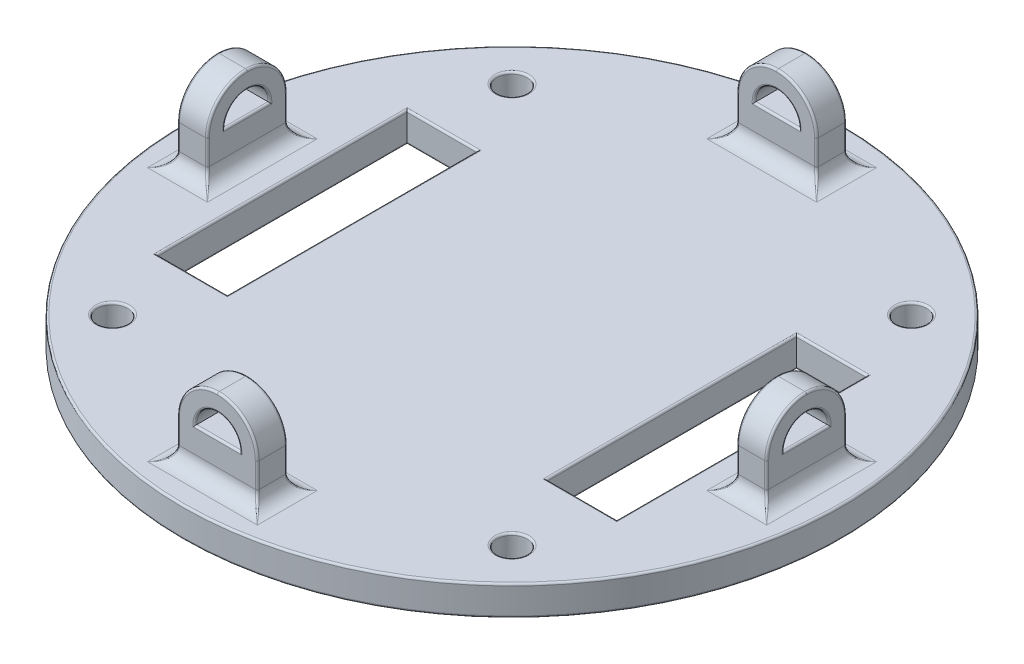
SolidWorks part; units mm, degrees
ref_plane "Front Plane" through (0, 0, 0) normal (0, 0, 1) x (1, 0, 0)
ref_plane "Top Plane" through (0, 0, 0) normal (0, 1, 0) x (1, 0, 0)
ref_plane "Right Plane" through (0, 0, 0) normal (1, 0, 0) x (0, 0, -1)
sketch "Sketch1" plane through (0, 0, 0) normal (0, 1, 0) x (1, 0, 0)
  circle A0 centre (0, 0) radius 33
  dimension "D1" = 66
extrude "Boss-Extrude1" add sketch "Sketch1" along normal blind 3
sketch "Sketch2" plane through (0, 3, 0) normal (0, 1, 0) x (1, 0, 0)
  line L0 (0, -6.05) -> (0, 6.05) construction
  line L1 (-23, 12.5) -> (-16, 12.5)
  line L2 (-23, 12.5) -> (-23, -12.5)
  line L3 (-23, -12.5) -> (-16, -12.5)
  line L4 (-16, 12.5) -> (-16, -12.5)
  line L9 (16, 12.5) -> (16, -12.5)
  line L10 (23, -12.5) -> (16, -12.5)
  line L11 (23, 12.5) -> (23, -12.5)
  line L12 (23, 12.5) -> (16, 12.5)
  point P8 (-16, 0)
  dimension "D1" = 7
  dimension "D2" = 25
  dimension "D3" = 16
extrude "Cut-Extrude1" cut sketch "Sketch2" against normal up to next
sketch "Sketch3" plane through (0, 3, 0) normal (0, 1, 0) x (1, 0, 0)
  line L0 (0, -6.05) -> (0, 6.05) construction
  line L1 (-6.05, 0) -> (6.05, 0) construction
  circle A0 centre (-20, -20) radius 1.5
  circle A4 centre (20, -20) radius 1.5
  circle A5 centre (20, 20) radius 1.5
  circle A6 centre (-20, 20) radius 1.5
  point P12 (0, 0)
  dimension "D3" = 3
  dimension "D1" = 20
  dimension "D2" = 20
extrude "Cut-Extrude2" cut sketch "Sketch3" against normal up to next
sketch "Sketch4" plane through (0, 3, 0) normal (0, 1, 0) x (1, 0, 0)
  line L5 (-4, 29.5) -> (4, 29.5)
  line L6 (-4, 29.5) -> (-4, 26.5)
  line L7 (-4, 26.5) -> (4, 26.5)
  line L8 (4, 29.5) -> (4, 26.5)
  line L9 (0, 26.5) -> (0, 29.5) construction
  line L10 (-4, 28) -> (4, 28) construction
  point P0 (0, 28)
  dimension "D1" = 3
  dimension "D2" = 8
  dimension "D3" = 28
extrude "Boss-Extrude2" add sketch "Sketch4" along normal blind 8
sketch "Sketch5" plane through (0, 0, -26.5) normal (0, 0, 1) x (1, 0, 0)
  line L0 (-4, 11) -> (4, 11) construction
  line L1 (-2.25, 7) -> (2.25, 7)
  arc A0 (2.25, 7) -> (-2.25, 7) centre (0, 7) ccw
  dimension "D1" = 4.5
  dimension "D2" = 4
extrude "Cut-Extrude3" cut sketch "Sketch5" against normal up to next
fillet "Fillet1" radius 4 2 edges at (-4, 11, -28) (4, 11, -28)
fillet "Fillet2" radius 1.5 4 edges at (0, 3, -29.5) (0, 3, -26.5) (-4, 3, -28) (4, 3, -28)
fillet "Fillet5" radius 0.2 16 edges at (4.4393, 3.4393, -29.9393) (4, 5.75, -29.5) (2.8284, 9.8284, -29.5) (-2.8284, 9.8284, -29.5) (-4, 5.75, -29.5) (4.4393, 3.4393, -26.0607) (4, 5.75, -26.5) (2.8284, 9.8284, -26.5) (-2.8284, 9.8284, -26.5) (-4, 5.75, -26.5) (-4.4393, 3.4393, -29.9393) (-4.4393, 3.4393, -26.0607) (0, 9.25, -29.5) (0, 7, -29.5) (0, 9.25, -26.5) (0, 7, -26.5)
pattern_circular "CirPattern1" count 4 over 360 about axis through (0, 3, 0) along (0, 1, 0) of "Boss-Extrude2", "Cut-Extrude3", "Fillet1", "Fillet2", "Fillet5"
fillet "Fillet4" radius 0.2 26 edges at (0, 0, 33) (19.5, 0, 12.5) (16, 0, 0) (19.5, 0, -12.5) (23, 0, 0) (-16, 0, 0) (-19.5, 0, 12.5) (-23, 0, 0) (-19.5, 0, -12.5) (-20, 0, 21.5) (20, 0, 21.5) (20, 0, -18.5) (-20, 0, -18.5) (0, 3, 33) (16, 3, 0) (19.5, 3, 12.5) (23, 3, 0) (19.5, 3, -12.5) (-19.5, 3, 12.5) (-16, 3, 0) (-19.5, 3, -12.5) (-23, 3, 0) (-20, 3, 21.5) (20, 3, 18.5) (20, 3, -18.5) (-20, 3, -21.5)
equation "\"D1@Sketch3\"=\"D2@Sketch3\""
